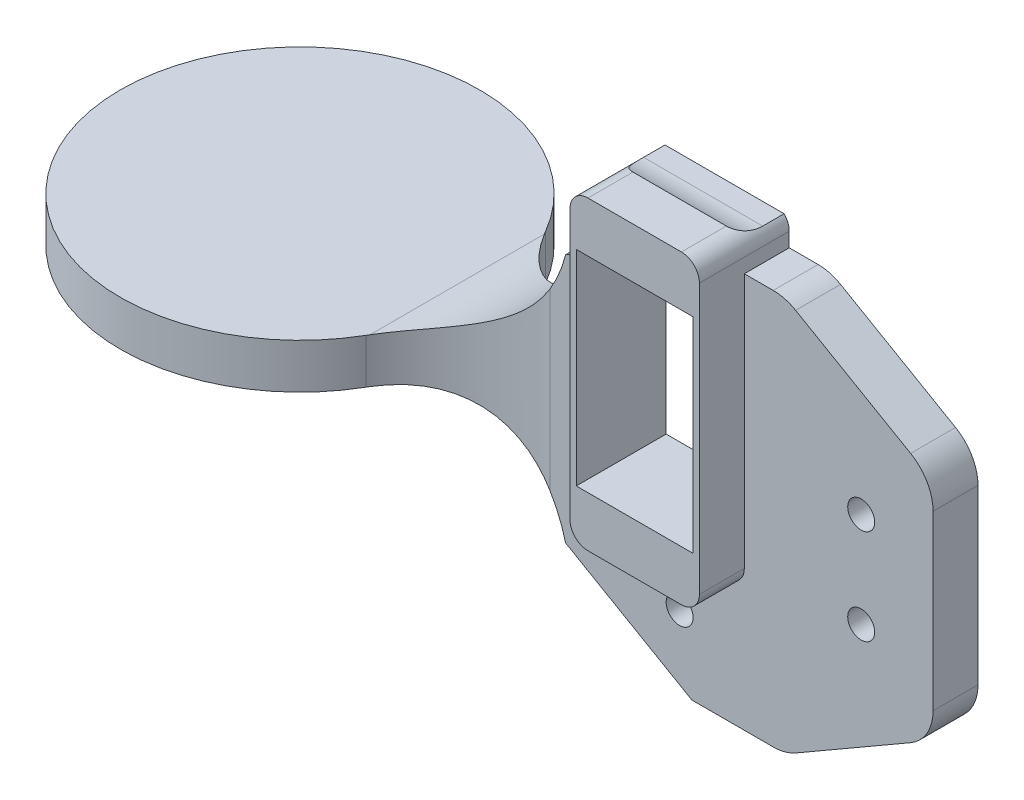
SolidWorks part; units mm, degrees
material "ABS"
ref_plane "Front Plane" through (0, 0, 0) normal (0, 0, 1) x (1, 0, 0)
ref_plane "Top Plane" through (0, 0, 0) normal (0, 1, 0) x (1, 0, 0)
ref_plane "Right Plane" through (0, 0, 0) normal (1, 0, 0) x (0, 0, -1)
other "Center of Mass"
sketch "Sketch1" plane through (0, 0, 0) normal (0, 1, 0) x (1, 0, 0)
  line L0 (0, 0) -> (128.1157, 0) construction
  line L2 (30.3109, -2.5) -> (82.5, -2.5)
  line L4 (30.3109, 2.5) -> (82.5, 2.5)
  line L5 (82.5, -2.5) -> (82.5, 2.5)
  arc A0 (17.3205, 10) -> (17.3205, -10) centre (0, 0) ccw
  arc A1 (30.3109, 2.5) -> (17.3205, 10) centre (30.3109, 17.5) cw
  arc A2 (17.3205, -10) -> (30.3109, -2.5) centre (30.3109, -17.5) cw
  point P3 (50, 0)
  dimension "D1" = 40
  dimension "D4" = 15
  dimension "D5" = 15
  dimension "D2" = 5
  dimension "D3" = 82.5
extrude "Boss-Extrude1" add sketch "Sketch1" along normal blind 5
sketch "Sketch4" plane through (82.5, 0, 0) normal (1, 0, 0) x (0, 0, -1)
  line L0 (0, 5) -> (0, 0) construction
  line L1 (-2.5, 5) -> (2.5, 5) construction
  line L3 (-2.5, -22.5) -> (2.5, -22.5)
  line L4 (-2.5, -22.5) -> (-2.5, 27.5)
  line L5 (-2.5, 27.5) -> (2.5, 27.5)
  line L6 (2.5, -22.5) -> (2.5, 27.5)
  line L7 (-2.5, -22.5) -> (2.5, 27.5) construction
  line L8 (-2.5, 27.5) -> (2.5, -22.5) construction
  point P5 (0, 2.5)
  dimension "D1" = 50
  dimension "D2" = 5
extrude "Boss-Extrude4" add sketch "Sketch4" against normal blind 50
fillet "Fillet1" radius 15 2 edges at (32.5, 0, 0) (32.5, 5, 0)
sketch "Sketch5" plane through (0, 0, 2.5) normal (0, 0, 1) x (1, 0, 0)
  line L0 (82.5, 2.5) -> (30.3109, 2.5) construction
  line L1 (82.5, 27.5) -> (82.5, -22.5) construction
  line L2 (30.3109, 12.1974) -> (30.3109, -7.1974) construction
  line L3 (57.5, 27.5) -> (57.5, -22.5) construction
  line L4 (32.5, 27.5) -> (82.5, 27.5) construction
  line L5 (32.5, -22.5) -> (82.5, -22.5) construction
  line L6 (56.4054, 2.5) -> (30.3109, 2.5) construction
  line L7 (32.5, 27.5) -> (32.5, 20) construction
  line L8 (32.5, 28.75) -> (57, 28.75)
  line L9 (32.5, 28.75) -> (32.5, -23.75)
  line L10 (32.5, -23.75) -> (57, -23.75)
  line L11 (57, 28.75) -> (57, -23.75)
  line L12 (32.5, 28.75) -> (57, -23.75) construction
  line L13 (32.5, -23.75) -> (57, 28.75) construction
  line L14 (44.75, -23.75) -> (44.75, 28.75) construction
  line L15 (38.25, -0.3) -> (51.25, 22.5) construction
  line L16 (38.25, 22.5) -> (51.25, 22.5)
  line L17 (38.25, 22.5) -> (38.25, -0.3)
  line L18 (38.25, -0.3) -> (51.25, -0.3)
  line L19 (51.25, 22.5) -> (51.25, -0.3)
  line L20 (38.25, 11.1) -> (51.25, 11.1) construction
  line L21 (51.95, -5.9) -> (37.55, -5.9)
  line L22 (51.95, -5.9) -> (51.95, 28.1)
  line L23 (51.95, 28.1) -> (37.55, 28.1)
  line L24 (37.55, -5.9) -> (37.55, 28.1)
  line L25 (51.95, -5.9) -> (37.55, 28.1) construction
  line L26 (51.95, 28.1) -> (37.55, -5.9) construction
  circle A0 centre (44.75, 16.5) radius 12.25
  circle A1 centre (44.75, -11.5) radius 12.25
  circle A2 centre (44.75, -11.5) radius 15.75
  circle A3 centre (64.9562, -2.7988) radius 1.5
  circle A4 centre (64.9562, -2.7988) radius 3
  circle A5 centre (64.9562, 7.7988) radius 3
  circle A6 centre (64.9562, 7.7988) radius 1.5
  circle A7 centre (44.75, -11.5) radius 1.5
  circle A8 centre (44.75, -11.5) radius 3
  point P13 (44.75, 2.5)
  point P30 (44.75, 11.1)
  dimension "D4" = 12.25
  dimension "D5" = 24.5
  dimension "D13" = 31.5
  dimension "D14" = 3
  dimension "D16" = 6
  dimension "D17" = 22
  dimension "D18" = 3
  dimension "D19" = 6
  dimension "D1" = 24.5
  dimension "D2" = 52.5
  dimension "D3" = 0
  dimension "D6" = 12.25
  dimension "D7" = 6
  dimension "D8" = 22.8
  dimension "D9" = 13
  dimension "D10" = 34
  dimension "D11" = 14.4
  dimension "D12" = 5.6
  dimension "D15" = 5.2988
sketch "Sketch6" plane through (0, 0, 2.5) normal (0, 0, 1) x (1, 0, 0)
  circle A0 centre (44.75, -11.5) radius 1.5
  dimension "D1" = 3
extrude "Cut-Extrude1" cut sketch "Sketch6" against normal through all
sketch "Sketch8" plane through (0, 0, 2.5) normal (0, 0, 1) x (1, 0, 0)
  line L0 (37.55, -5.9) -> (37.55, 28.1)
  line L1 (37.55, 28.1) -> (51.95, 28.1)
  line L2 (51.95, 28.1) -> (51.95, -5.9)
  line L3 (51.95, -5.9) -> (37.55, -5.9)
  dimension "D1" = 34
extrude "Boss-Extrude5" add sketch "Sketch8" along normal blind 5
sketch "Sketch9" plane through (0, 0, 7.5) normal (0, 0, 1) x (1, 0, 0)
  line L0 (38.25, 22.5) -> (51.25, 22.5)
  line L1 (51.25, 22.5) -> (51.25, -0.3)
  line L2 (51.25, -0.3) -> (38.25, -0.3)
  line L3 (38.25, -0.3) -> (38.25, 22.5)
extrude "Cut-Extrude2" cut sketch "Sketch9" against normal through all
fillet "Fillet2" radius 5 2 edges at (32.5, -22.5, 0) (32.5, 27.5, 0)
fillet "Fillet3" radius 2 4 edges at (51.95, -5.9, 5) (51.95, 28.1, 5) (37.55, 28.1, 5) (37.55, -5.9, 5)
fillet "Fillet4" radius 6 1 edges at (44.75, 27.5, 2.5)
sketch "Sketch10" plane through (0, 0, -2.5) normal (0, 0, -1) x (-1, 0, 0)
  circle A0 centre (-64.9562, -2.7988) radius 1.5
  circle A1 centre (-64.9562, 7.7988) radius 1.5
  dimension "D1" = 3
  dimension "D2" = 3
extrude "Cut-Extrude3" cut sketch "Sketch10" against normal through all
sketch "Sketch14" plane through (0, 0, 2.5) normal (0, 0, 1) x (1, 0, 0)
  line L0 (72.9562, 27.5) -> (72.9562, -22.5)
  line L1 (82.5, -22.5) -> (28.5, -22.5)
  line L2 (82.5, -22.5) -> (82.5, -19.5)
  line L3 (56.5017, -19.5) -> (28.5, -19.5)
  line L4 (28.5, -22.5) -> (28.5, -19.5)
  line L5 (51.3783, 27.5) -> (82.5, 27.5) construction
  line L6 (56.5017, 24.5) -> (28.5, 24.5)
  line L7 (82.5, 2.5) -> (17.3205, 2.5) construction
  line L8 (17.3205, 5) -> (17.3205, 0) construction
  line L9 (51.3055, 27.5) -> (29.6549, 15)
  line L10 (29.6549, 15) -> (29.6549, -10)
  line L11 (29.6549, -10) -> (51.3055, -22.5)
  line L12 (51.3055, -22.5) -> (72.9562, -10)
  line L13 (72.9562, -10) -> (72.9562, 15)
  line L14 (72.9562, 15) -> (51.3055, 27.5)
  circle A0 centre (51.3055, 2.5) radius 21.6506 construction
  circle A1 centre (64.9562, 7.7988) radius 3 construction
  line M5 (32.5, -15) -> (32.5, -17.5)
  arc M6 (32.5, -17.5) -> (37.5, -22.5) centre (37.5, -17.5) ccw
  line M7 (37.5, -22.5) -> (82.5, -22.5)
  line M8 (82.5, -22.5) -> (82.5, 27.5)
  line M9 (82.5, 27.5) -> (51.3783, 27.5)
  arc M10 (51.3783, 27.5) -> (51.95, 26.1) centre (49.95, 26.1) cw
  line M11 (51.95, 26.1) -> (51.95, -3.9)
  line M15 (37.55, -3.9) -> (37.55, 26.1)
  arc M16 (37.55, 26.1) -> (38.1217, 27.5) centre (39.55, 26.1) cw
  line M17 (38.1217, 27.5) -> (37.5, 27.5)
  arc M18 (37.5, 27.5) -> (32.5, 22.5) centre (37.5, 22.5) ccw
  line M19 (32.5, 22.5) -> (32.5, 20)
  arc M20 (32.5, 20) -> (30.3109, 12.1974) centre (17.5, 20) cw
  arc M24 (30.3109, -7.1974) -> (32.5, -15) centre (17.5, -15) cw
  dimension "D4" = 8
  dimension "D6" = 25
  dimension "D1" = 3
  dimension "D2" = 8
  dimension "D3" = 54
  dimension "D5" = 0
extrude "Cut-Extrude6" cut sketch "Sketch14" against normal blind 10 contours L11 L3 M24 M5 M6 | L11 L3 M6 M7 | L12 L1 L0 | L11 L12 L3 | L0 M9 M7 M8 | L14 L0 M9 M10 | L6 L14 M10 M11 | L9 L6 M15 M18 M19 M20 | L6 M15 M16 M17 M18 region at (77.7281, 2.5, 2.5) region at (65.7396, 23.3332, 2.5) region at (65.7393, -18.3333, 2.5) region at (53.4314, 25.4107, 2.5) region at (51.3055, -20.5, 2.5) region at (41.4922, -21.0298, 2.5) region at (37.0179, -16.8305, 2.5) region at (34.8161, 21.1656, 2.5) region at (35.7594, 25.7757, 2.5)
fillet "Fillet5" radius 5 4 edges at (56.5017, 24.5, 0) (72.9562, 15, 0) (72.9562, -10, 0) (56.5017, -19.5, 0)
